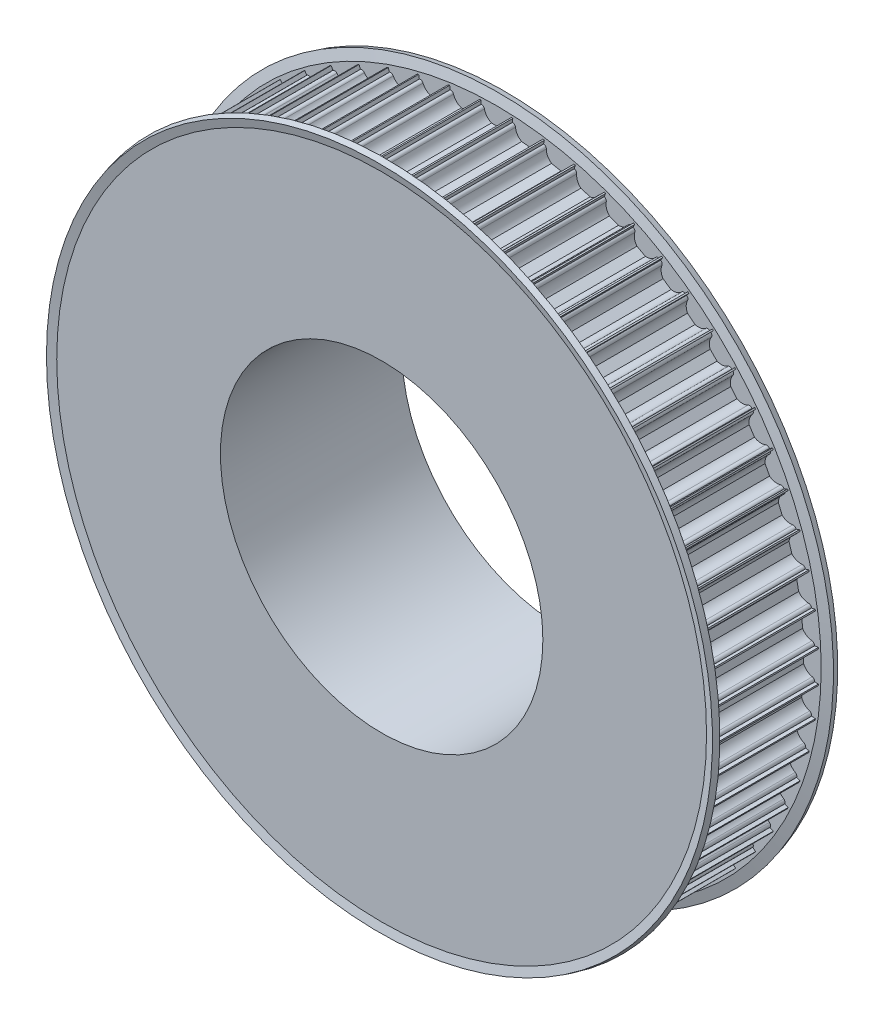
SolidWorks part; units mm, degrees
ref_plane "Front Plane" through (0, 0, 0) normal (0, 0, 1) x (1, 0, 0)
ref_plane "Top Plane" through (0, 0, 0) normal (0, 1, 0) x (1, 0, 0)
ref_plane "Right Plane" through (0, 0, 0) normal (1, 0, 0) x (0, 0, -1)
sketch "Sketch1" plane through (0, 0, 0) normal (1, 0, 0) x (0, 0, -1)
  line L0 (0, 0) -> (27.912, 0) construction
  line L1 (-5, 40) -> (40, 40)
  line L2 (40, 40) -> (40, 55.5)
  line L3 (40, 55.5) -> (25, 55.5)
  line L4 (25, 55.5) -> (25, 80)
  line L5 (25, 80) -> (-5, 80)
  line L6 (-5, 80) -> (-5, 40)
  dimension "D1" = 80
  dimension "D2" = 40
  dimension "D3" = 30
  dimension "D4" = 15
  dimension "D5" = 15.5
revolve "Revolve1" add sketch "Sketch1" angle 360 about L0
sketch "Sketch2" plane through (0, 0, 5) normal (0, 0, 1) x (1, 0, 0)
  line L0 (-3.6742, 79) -> (-3.75, 79)
  line L1 (-3.75, 79) -> (-3.75, 81)
  line L2 (-3.75, 81) -> (3.75, 81)
  line L3 (3.75, 81) -> (3.75, 79)
  line L4 (3.75, 79) -> (3.6742, 79)
  line L5 (-1.199, 76.25) -> (1.199, 76.25)
  arc A0 (2.9394, 78.4) -> (1.199, 76.25) centre (0, 79) cw
  arc A1 (2.9394, 78.4) -> (3.6742, 79) centre (3.6742, 78.25) cw
  arc A2 (-2.9394, 78.4) -> (-3.6742, 79) centre (-3.6742, 78.25) ccw
  arc A3 (-1.199, 76.25) -> (-2.9394, 78.4) centre (0, 79) cw
  point P8 (0, 81)
  point P11 (3, 79)
  point P14 (-3, 79)
  dimension "D1" = 3
  dimension "D5" = 0.75
  dimension "D2" = 79
  dimension "D3" = 7.5
  dimension "D4" = 2
  dimension "D6" = 2.75
extrude "Cut-Extrude1" cut sketch "Sketch2" against normal up to next
pattern_circular "CirPattern1" count 64 over 360 about axis through (0, 0, 5) along (0, 0, 1) of "Cut-Extrude1"
sketch "Sketch3" plane through (0, 0, 0) normal (1, 0, 0) x (0, 0, -1)
  line L0 (10, -40.9775) -> (10, -16.0516) construction
  line L1 (25, -40.9775) -> (-5, -40.9775) construction
  line L2 (25, -16.0516) -> (-5, -16.0516) construction
  line L4 (25, 80.61) -> (25.5391, 82.6218)
  line L5 (25.5391, 82.6218) -> (24.0902, 83.01)
  line L6 (24.0902, 83.01) -> (23.4471, 80.61)
  line L7 (23.4471, 80.61) -> (23.4471, 55.5)
  line L8 (23.4471, 55.5) -> (25, 55.5)
  line L9 (40, 55.5) -> (25, 55.5) construction
  line L10 (25, 80.61) -> (25, 55.5)
  line L11 (-5, 80.61) -> (-5.5391, 82.6218)
  line L12 (-5.5391, 82.6218) -> (-4.0902, 83.01)
  line L13 (-4.0902, 83.01) -> (-3.4471, 80.61)
  line L14 (-3.4471, 80.61) -> (-3.4471, 55.5)
  line L15 (-3.4471, 55.5) -> (-5, 55.5)
  line L16 (-5, 80.61) -> (-5, 55.5)
  line L17 (0, 0) -> (-12.9451, 0) construction
  line L18 (-5, 62.4687) -> (-5, 59.7027) construction
  point P24 (-4.3116, 55.5)
  point P27 (25, 80.61)
  dimension "D1" = 195
  dimension "D2" = 1.5
  dimension "D3" = 25.11
  dimension "D4" = 2.4
revolve "Revolve2" add sketch "Sketch3" angle 360 about L17
